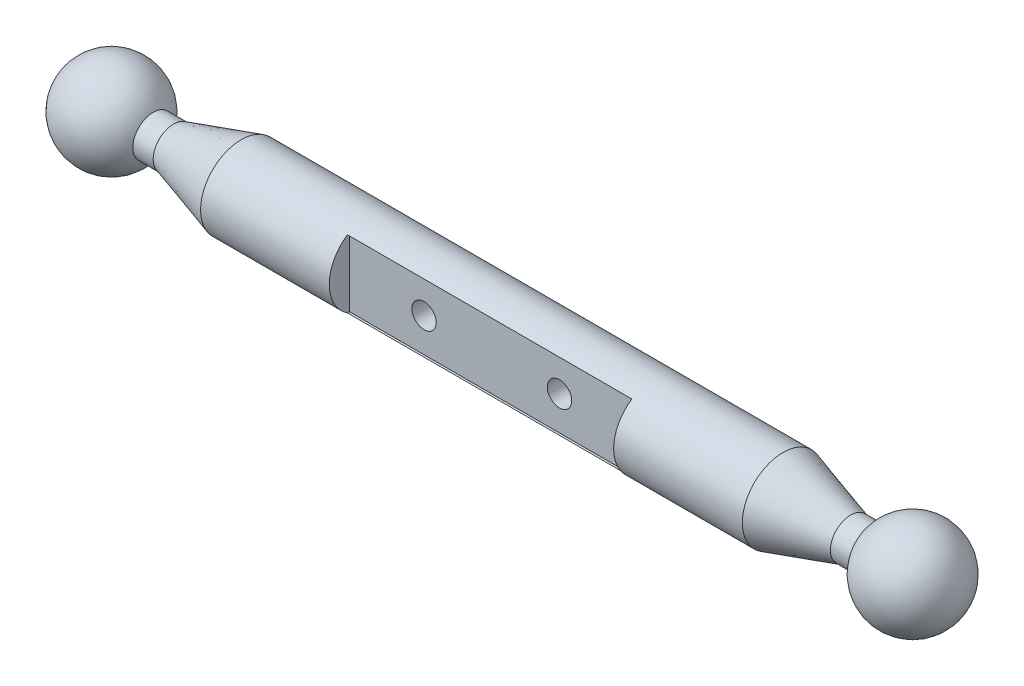
SolidWorks part; units mm, degrees
ref_plane "Front Plane" through (0, 0, 0) normal (0, 0, 1) x (1, 0, 0)
ref_plane "Top Plane" through (0, 0, 0) normal (0, 1, 0) x (1, 0, 0)
ref_plane "Right Plane" through (0, 0, 0) normal (1, 0, 0) x (0, 0, -1)
sketch "Sketch2" plane through (0, 0, 0) normal (0, 0, 1) x (1, 0, 0)
  line L0 (-265, 0) -> (265, 0)
  line L1 (265, 0) -> (265, 15)
  line L2 (265, 15) -> (250, 15)
  line L4 (-200, 30) -> (200, 30)
  line L5 (200, 30) -> (250, 15)
  line L7 (-200, 30) -> (-250, 15)
  line L8 (-265, 15) -> (-250, 15)
  line L9 (-265, 0) -> (-265, 15)
  dimension "D5" = 50
  dimension "D2" = 15
  dimension "D3" = 15
revolve "Revolve1" add sketch "Sketch2" angle 360 about L0
ref_plane "Plane1" through (0, 0, 30) normal (0, 0, 1) x (1, 0, 0)
sketch "Sketch4" plane through (0, 0, 30) normal (0, 0, 1) x (1, 0, 0)
  line L1 (-105, -25) -> (105, -25)
  line L2 (-105, -25) -> (-105, 25)
  line L3 (-105, 25) -> (105, 25)
  line L4 (105, -25) -> (105, 25)
  line L5 (-105, -25) -> (105, 25) construction
  line L6 (-105, 25) -> (105, -25) construction
  point P0 (0, 0)
  dimension "D1" = 210
  dimension "D2" = 50
extrude "Cut-Extrude2" cut sketch "Sketch4" against normal blind 15
sketch "Sketch5" plane through (0, 0, 30) normal (0, 0, 1) x (1, 0, 0)
  circle A0 centre (50, 0) radius 9
  circle A1 centre (-50, 0) radius 9
  point P4 (0, 0)
  dimension "D1" = 50
  dimension "D3" = 18
  dimension "D4" = 18
  dimension "D2" = 50
extrude "Cut-Extrude3" cut sketch "Sketch5" against normal blind 80
dome "Dome1" faces to dome 1 distance 65 reverse direction no elliptical dome no face at (265, 0, 15) parameters "D1"=65
dome "Dome2" faces to dome 1 distance 65 reverse direction no elliptical dome no face at (-265, 0, 15) parameters "D1"=65
